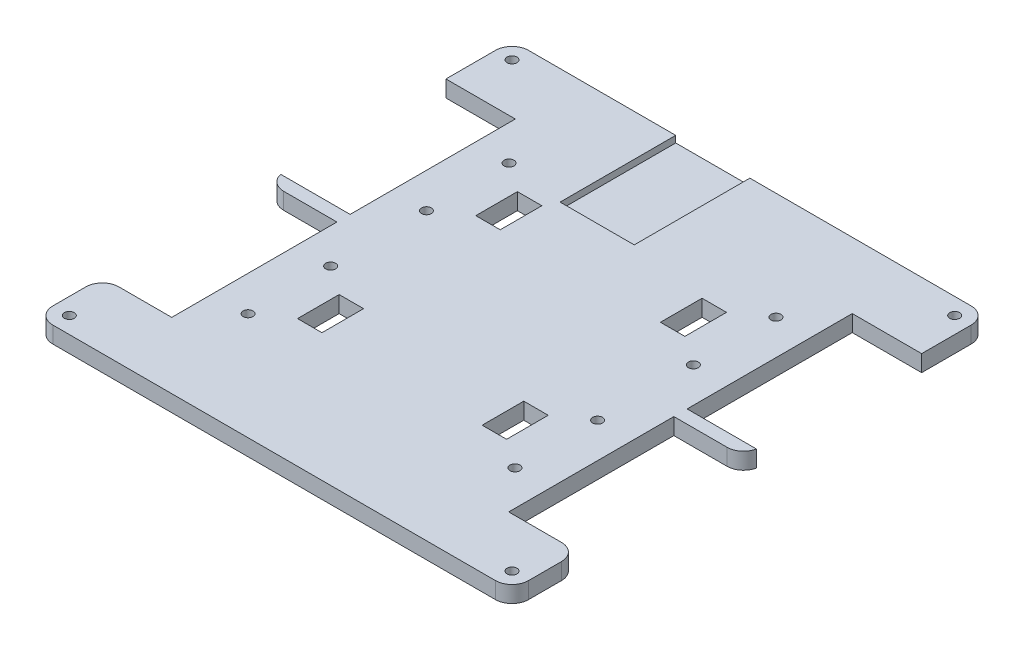
SolidWorks part; units mm, degrees
ref_plane "Front Plane" through (0, 0, 0) normal (0, 0, 1) x (1, 0, 0)
ref_plane "Top Plane" through (0, 0, 0) normal (0, 1, 0) x (1, 0, 0)
ref_plane "Right Plane" through (0, 0, 0) normal (1, 0, 0) x (0, 0, -1)
sketch "Sketch1" plane through (0, 0, 0) normal (0, 1, 0) x (1, 0, 0)
  line L1 (-72, 72) -> (72, 72)
  line L2 (-72, 72) -> (-72, -72)
  line L3 (-72, -72) -> (72, -72)
  line L4 (72, 72) -> (72, -72)
  point P0 (0, 0)
  dimension "D1" = 144
  dimension "D2" = 144
  dimension "D3" = 72
  dimension "D4" = 72
extrude "Boss-Extrude1" add sketch "Sketch1" along normal blind 5
sketch "Sketch2" plane through (0, 5, 0) normal (0, 1, 0) x (1, 0, 0)
  line L0 (0, 0) -> (77.0703, 0) construction
  line L1 (-72, -2) -> (-72, -52)
  line L2 (-72, 72) -> (-72, -72) construction
  line L3 (-72, -52) -> (-51, -52)
  line L4 (-51, -52) -> (-51, -2)
  line L5 (-51, -2) -> (-72, -2)
  line L6 (0, 72) -> (0, -72) construction
  line L7 (72, 72) -> (-72, 72) construction
  line L8 (-72, -72) -> (72, -72) construction
  line L9 (51, -2) -> (72, -2)
  line L10 (51, -52) -> (51, -2)
  line L11 (72, -52) -> (51, -52)
  line L12 (72, -2) -> (72, -52)
  line L13 (72, 2) -> (72, 52)
  line L14 (51, 2) -> (72, 2)
  line L15 (51, 52) -> (51, 2)
  line L16 (72, 52) -> (51, 52)
  line L17 (-72, 52) -> (-51, 52)
  line L18 (-51, 52) -> (-51, 2)
  line L19 (-51, 2) -> (-72, 2)
  line L20 (-72, 2) -> (-72, 52)
  point P11 (0, 0)
  dimension "D1" = 21
  dimension "D2" = 50
  dimension "D3" = 52
extrude "Cut-Extrude1" cut sketch "Sketch2" against normal blind 5
sketch "Sketch11" plane through (0, 5, 0) normal (0, 1, 0) x (1, 0, 0)
  line L0 (31.6454, -20.6825) -> (24.2454, -20.6825)
  line L1 (24.2454, -20.6825) -> (24.2454, -33.2825)
  line L2 (24.2454, -33.2825) -> (31.6454, -33.2825)
  line L3 (31.6454, -33.2825) -> (31.6454, -20.6825)
  line L4 (-72, 0) -> (72, 0) construction
  line L5 (0, -72) -> (0, 76.313) construction
  line L6 (-72, -72) -> (72, -72) construction
  line L7 (-24.2454, -20.6825) -> (-24.2454, -33.2825)
  line L8 (-31.6454, -20.6825) -> (-24.2454, -20.6825)
  line L9 (-31.6454, -33.2825) -> (-31.6454, -20.6825)
  line L10 (-24.2454, -33.2825) -> (-31.6454, -33.2825)
  line L11 (-72, 2) -> (-72, -2) construction
  line L12 (72, -2) -> (72, 2) construction
  line L13 (24.2454, 33.2825) -> (31.6454, 33.2825)
  line L14 (24.2454, 20.6825) -> (24.2454, 33.2825)
  line L15 (31.6454, 20.6825) -> (24.2454, 20.6825)
  line L16 (31.6454, 33.2825) -> (31.6454, 20.6825)
  line L17 (-31.6454, 20.6825) -> (-24.2454, 20.6825)
  line L18 (-31.6454, 33.2825) -> (-31.6454, 20.6825)
  line L19 (-24.2454, 33.2825) -> (-31.6454, 33.2825)
  line L20 (-24.2454, 20.6825) -> (-24.2454, 33.2825)
  dimension "D1" = 12.6
  dimension "D2" = 7.4
  dimension "D3" = 20.6825
  dimension "D4" = 24.2454
extrude "Cut-Extrude10" cut sketch "Sketch11" against normal up to surface (5 mm away) up to face at (0, 0, 0)
sketch "Sketch13" plane through (0, 5, 0) normal (0, 1, 0) x (1, 0, 0)
  line L0 (0, 72) -> (0, -72) construction
  line L2 (72, 72) -> (-72, 72) construction
  line L3 (-72, -72) -> (72, -72) construction
  line L4 (-72, 0) -> (72, 0) construction
  line L5 (-72, 72) -> (-72, 52) construction
  line L6 (72, -2) -> (72, 2) construction
  circle A0 centre (-67, 67) radius 1.5
  circle A1 centre (-67, -67) radius 1.5
  circle A2 centre (67, 67) radius 1.5
  circle A3 centre (67, -67) radius 1.5
  dimension "D1" = 5
  dimension "D3" = 3
  dimension "D2" = 5
extrude "Cut-Extrude12" cut sketch "Sketch13" against normal up to surface (5 mm away) up to face at (-27.9454, 0, 26.9825)
fillet "Fillet1" radius 5 1 edges at (-72, 2.5, -72)
fillet "Fillet2" radius 5 3 edges at (-72, 2.5, 72) (-72, 2.5, 2) (-72, 2.5, 52)
fillet "Fillet3" radius 5 4 edges at (72, 2.5, -72) (72, 2.5, 2) (72, 2.5, 52) (72, 2.5, 72)
sketch "Sketch14" plane through (0, 0, 0) normal (0, -1, 0) x (1, 0, 0)
  circle A0 centre (-40.4, 39.5) radius 1.5
  circle A1 centre (-40.4, 14.5) radius 1.5
  circle A2 centre (40.4, 39.5) radius 1.5
  circle A3 centre (40.4, 14.5) radius 1.5
  circle A4 centre (-40.4, -14.5) radius 1.5
  circle A5 centre (-40.4, -39.5) radius 1.5
  circle A6 centre (40.4, -14.5) radius 1.5
  circle A7 centre (40.4, -39.5) radius 1.5
  dimension "D1" = 3
extrude "Cut-Extrude13" cut sketch "Sketch14" against normal up to surface (5 mm away) up to face at (-67, 5, 65.5)
sketch "Sketch15" plane through (0, 5, 0) normal (0, 1, 0) x (1, 0, 0)
  line L0 (-22.44, 72) -> (-22.44, 37)
  line L1 (67, 72) -> (-67, 72) construction
  line L2 (-22.44, 72) -> (0, 72)
  line L3 (-22.44, 37) -> (0, 37)
  line L4 (0, 37) -> (0, 72)
  point P8 (-11.22, 72)
  dimension "D1" = 43.273
  dimension "D2" = 37
  dimension "D3" = 0
  dimension "D4" = 22.44
  dimension "D5" = 72
extrude "Cut-Extrude14" cut sketch "Sketch15" against normal blind 2
